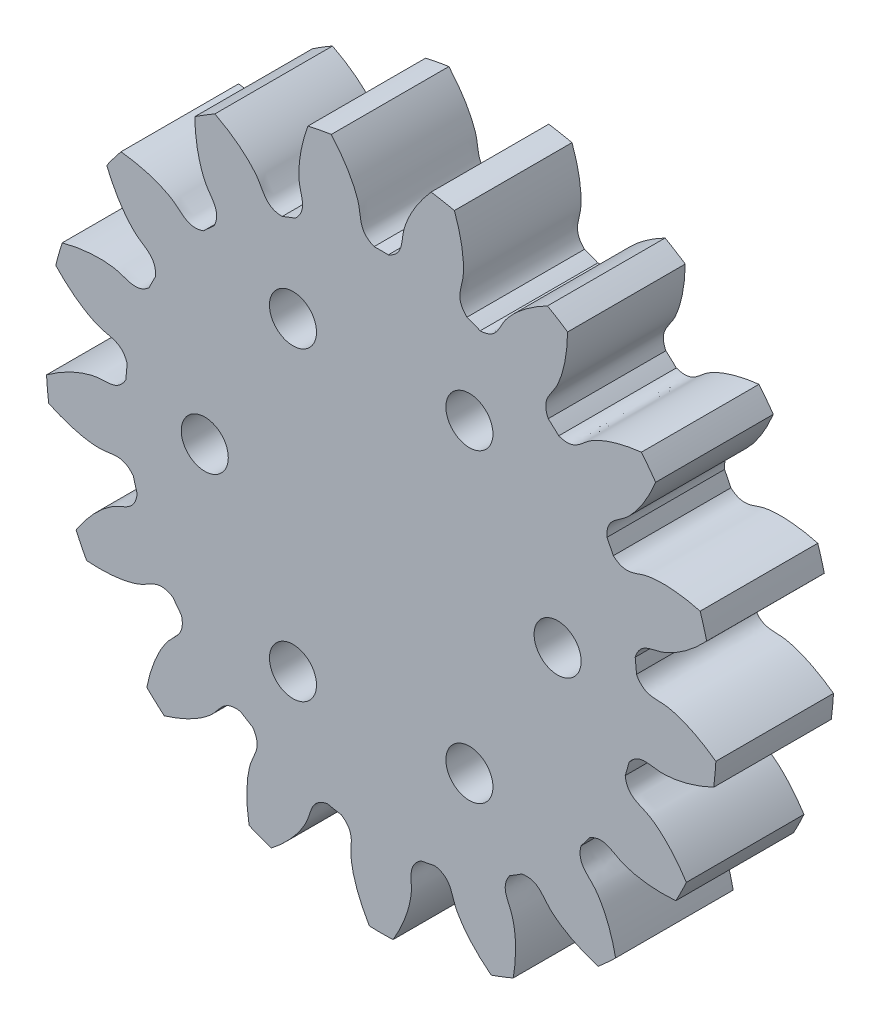
SolidWorks part; units mm, degrees
material "POM 乙缩醛共聚物"
ref_plane "前视基准面" through (0, 0, 0) normal (0, 0, 1) x (1, 0, 0)
ref_plane "上视基准面" through (0, 0, 0) normal (0, 1, 0) x (1, 0, 0)
ref_plane "右视基准面" through (0, 0, 0) normal (1, 0, 0) x (0, 0, -1)
sketch "草图1" plane through (0, 0, 0) normal (0, 0, 1) x (1, 0, 0)
  circle A0 centre (0, 0) radius 28.5
extrude "凸台-拉伸1" add sketch "草图1" along normal blind 10
ref_axis "基准轴1" through (0, 0, 10) along (0, 0, -1)
sketch "草图2" plane through (0, 0, 0) normal (0, 0, 1) x (1, 0, 0)
  line L0 (0, 0) -> (0, 28.5) construction
  circle A0 centre (0, 0) radius 28.5 construction
  arc A1 (0.6051, 21.7416) -> (-0.6051, 21.7416) centre (0, 0) ccw
  arc A2 (9.3469, 32.2222) -> (-9.3469, 32.2222) centre (0, 0) ccw
  spline S0 degree 3 poles (0.6051, 21.7416) (1.8836, 22.2745) (1.6986, 23.2644) (1.9149, 24.1945) (1.9349, 24.2735) (1.9591, 24.3613) (1.9877, 24.4578) (2.0211, 24.5628) (2.0597, 24.6762) (2.1038, 24.7979) (2.1538, 24.9276) (2.21, 25.0651) (2.2727, 25.2103) (2.3424, 25.3629) (2.4192, 25.5227) (2.5035, 25.6895) (2.5956, 25.8631) (2.6958, 26.0432) (2.8044, 26.2295) (2.9217, 26.4218) (3.048, 26.6198) (3.1836, 26.8232) (3.3286, 27.0317) (3.4835, 27.245) (3.6483, 27.4629) (3.8234, 27.6849) (4.009, 27.9108) (4.2053, 28.1402) (4.4126, 28.3728) (4.6309, 28.6082) (4.8606, 28.8462) (5.1018, 29.0862) (5.3546, 29.328) (5.6193, 29.5712) (5.896, 29.8154) (6.1849, 30.0602) (6.486, 30.3052) (6.7995, 30.55) (7.1255, 30.7943) (7.4641, 31.0376) (7.8154, 31.2795) (8.1795, 31.5197) (8.6875, 31.8403) (9.0797, 32.0716) (9.3469, 32.2222) knots 0 0 0 0 0.193883 0.199024 0.204851 0.211363 0.21856 0.226443 0.235011 0.244265 0.254205 0.264829 0.27614 0.288136 0.300817 0.314184 0.328236 0.342973 0.358397 0.374505 0.391299 0.408779 0.426944 0.445795 0.465331 0.485552 0.506459 0.528051 0.550329 0.573293 0.596941 0.621276 0.646296 0.672001 0.698392 0.725468 0.753229 0.781677 0.810809 0.840627 0.871131 0.90232 0.934195 1 1 1 1
  spline S1 degree 3 poles (-0.6051, 21.7416) (-1.8836, 22.2745) (-1.6986, 23.2644) (-1.9149, 24.1945) (-1.9349, 24.2735) (-1.9591, 24.3613) (-1.9877, 24.4578) (-2.0211, 24.5628) (-2.0597, 24.6762) (-2.1038, 24.7979) (-2.1538, 24.9276) (-2.21, 25.0651) (-2.2727, 25.2103) (-2.3424, 25.3629) (-2.4192, 25.5227) (-2.5035, 25.6895) (-2.5956, 25.8631) (-2.6958, 26.0432) (-2.8044, 26.2295) (-2.9217, 26.4218) (-3.048, 26.6198) (-3.1836, 26.8232) (-3.3286, 27.0317) (-3.4835, 27.245) (-3.6483, 27.4629) (-3.8234, 27.6849) (-4.009, 27.9108) (-4.2053, 28.1402) (-4.4126, 28.3728) (-4.6309, 28.6082) (-4.8606, 28.8462) (-5.1018, 29.0862) (-5.3546, 29.328) (-5.6193, 29.5712) (-5.896, 29.8154) (-6.1849, 30.0602) (-6.486, 30.3052) (-6.7995, 30.55) (-7.1255, 30.7943) (-7.4641, 31.0376) (-7.8154, 31.2795) (-8.1795, 31.5197) (-8.6875, 31.8403) (-9.0797, 32.0716) (-9.3469, 32.2222) knots 0 0 0 0 0.193883 0.199024 0.204851 0.211363 0.21856 0.226443 0.235011 0.244265 0.254205 0.264829 0.27614 0.288136 0.300817 0.314184 0.328236 0.342973 0.358397 0.374505 0.391299 0.408779 0.426944 0.445795 0.465331 0.485552 0.506459 0.528051 0.550329 0.573293 0.596941 0.621276 0.646296 0.672001 0.698392 0.725468 0.753229 0.781677 0.810809 0.840627 0.871131 0.90232 0.934195 1 1 1 1
extrude "切除-拉伸1" cut sketch "草图2" along normal through all
pattern_circular "阵列(圆周)1" count 17 every 21.176 about axis through (0, 0, 10) along (0, 0, -1) of "切除-拉伸1"
sketch "草图3" plane through (0, 0, 0) normal (0, 0, 1) x (1, 0, 0)
  circle A0 centre (0, 0) radius 25.5 construction
  dimension "Dn" = 51
sketch "草图4" plane through (0, 0, 10) normal (0, 0, 1) x (1, 0, 0)
  circle A0 centre (0, 0) radius 15 construction
  circle A1 centre (-15, 0) radius 2
  circle A2 centre (-7.5, 12.9904) radius 2
  circle A3 centre (7.5, 12.9904) radius 2
  circle A4 centre (15, 0) radius 2
  circle A5 centre (7.5, -12.9904) radius 2
  circle A6 centre (-7.5, -12.9904) radius 2
  point P17 (0, 0)
  dimension "D1" = 30
  dimension "D2" = 4
  dimension "D3" = 6
extrude "切除-拉伸2" cut sketch "草图4" against normal through all
